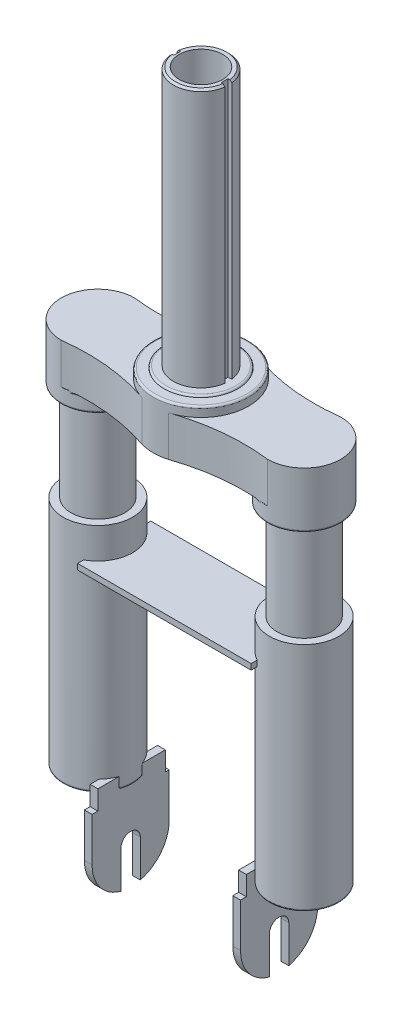
SolidWorks part; units mm, degrees
ref_plane "Front Plane" through (0, 0, 0) normal (0, 0, 1) x (1, 0, 0)
ref_plane "Top Plane" through (0, 0, 0) normal (0, 1, 0) x (1, 0, 0)
ref_plane "Right Plane" through (0, 0, 0) normal (1, 0, 0) x (0, 0, -1)
sketch "Sketch1" plane through (0, 0, 0) normal (0, 0, 1) x (1, 0, 0)
  line L0 (0, -70) -> (0, 70)
  point P4 (0, 0)
  dimension "D1" = 140
sketch "Sketch2" plane through (0, 0, 0) normal (0, 1, 0) x (1, 0, 0)
  circle A0 centre (0, 0) radius 14.3
  circle A1 centre (0, 0) radius 11.3
  dimension "D1" = 28.6
  dimension "D2" = 3
extrude "Boss-Extrude1" add sketch "Sketch2" against normal blind 140
sketch "Sketch3" plane through (0, -140, 0) normal (0, -1, 0) x (1, 0, 0)
  line L0 (-53.5, 0) -> (53.5, 0) construction
  line L5 (-72.5, 24.75) -> (72.5, -24.75) construction
  line L6 (-72.5, -24.75) -> (72.5, 24.75) construction
  line L7 (0, 58.8886) -> (0, -34.6433) construction
  circle A1 centre (0, 0) radius 17.2
  arc A2 (49.4574, -18.5649) -> (49.4574, 18.5649) centre (53.5, 0) ccw
  arc A3 (-49.4574, -18.5649) -> (-49.4574, 18.5649) centre (-53.5, 0) cw
  arc A4 (-8.7282, -23.1599) -> (8.7282, -23.1599) centre (0, 0) ccw
  arc A5 (-53.5, -19) -> (-6.9022, -23.7681) centre (-40.4353, -121.401) cw
  arc A6 (53.5, -19) -> (6.9022, -23.7681) centre (40.4353, -121.401) ccw
  arc A7 (53.5, 19) -> (6.9022, 23.7681) centre (40.4353, 121.401) cw
  arc A8 (-53.5, 19) -> (-6.9022, 23.7681) centre (-40.4353, 121.401) ccw
  arc A9 (8.7282, 23.1599) -> (-8.7282, 23.1599) centre (0, 0) ccw
  circle A10 centre (0, 0) radius 11.3 construction
  point P0 (0, 0)
  point P12 (0, 0)
  dimension "D1" = 103.231
  dimension "D3" = 34.4
  dimension "D4" = 38
  dimension "D5" = 49.5
  dimension "D2" = 6.9022
  dimension "D6" = 8.7282
  dimension "D7" = 72.5
  dimension "D8" = 24.75
  dimension "D9" = 93.5319
  dimension "D10" = 58.8886
extrude "Boss-Extrude4" add sketch "Sketch3" along normal blind 21 separate body contours A7 A9 A8 A3 A5 A4 A6 A2 A1 region at (28.6907, -140, -17.2982)
sketch "Sketch7" plane through (0, -140, 0) normal (0, 1, 0) x (1, 0, 0)
  circle A0 centre (0, 0) radius 24.75
  dimension "D1" = 49.5
extrude "Boss-Extrude5" add sketch "Sketch7" along normal blind 5
fillet "Fillet3" radius 1 1 edges at (0, -135, 24.75)
sketch "Sketch8" plane through (0, -135, 0) normal (0, 1, 0) x (1, 0, 0)
  circle A0 centre (0, 0) radius 19.15
  circle A1 centre (0, 0) radius 14.3 construction
  circle A2 centre (0, 0) radius 14.3
  dimension "D1" = 38.3
extrude "Boss-Extrude6" add sketch "Sketch8" along normal blind 0.9
fillet "Fillet4" radius 1 1 edges at (0, -134.1, 19.15)
sketch "Sketch9" plane through (0, -161, 0) normal (0, -1, 0) x (1, 0, 0)
  line L0 (-72.5, 0) -> (-53.5, 0) construction
  line L1 (0, 31.6889) -> (0, -24.75) construction
  arc A0 (-53.5, 19) -> (-53.5, -19) centre (-53.5, 0) ccw construction
  circle A1 centre (-53.5, 0) radius 19
  arc A2 (-6.9022, -23.7681) -> (6.9022, -23.7681) centre (0, 0) ccw construction
  circle A3 centre (53.5, 0) radius 19
  dimension "D1" = 38
extrude "Boss-Extrude7" add sketch "Sketch9" along normal blind 8.0064
fillet "Fillet5" radius 1 4 edges at (34.5, -161, 0) (53.5, -169.0064, 19) (-34.5, -161, 0) (-53.5, -169.0064, -19)
chamfer "Chamfer1" distance 1 angle 45 1 edges at (0, 0, 14.3)
sketch "Sketch10" plane through (0, -169.0064, 0) normal (0, -1, 0) x (1, 0, 0)
  line L0 (0, 39.8113) -> (0, -36.7225) construction
  circle A0 centre (-53.5, 0) radius 18 construction
  circle A1 centre (-53.5, 0) radius 18 construction
  circle A2 centre (-53.5, 0) radius 14
  circle A3 centre (53.5, 0) radius 14
  dimension "D1" = 28
extrude "Boss-Extrude8" add sketch "Sketch10" along normal blind 51.0064
fillet "Fillet7" radius 1 2 edges at (53.5, -169.0064, 14) (-53.5, -169.0064, -14)
sketch "Sketch11" plane through (0, -220.0128, 0) normal (0, -1, 0) x (1, 0, 0)
  line L0 (0, 38.6993) -> (0, -16.4417) construction
  circle A2 centre (-53.5, 0) radius 18
  circle A3 centre (-53.5, 0) radius 14 construction
  circle A4 centre (53.5, 0) radius 18
  dimension "D1" = 36
extrude "Boss-Extrude9" add sketch "Sketch11" along normal blind 120
fillet "Fillet8" radius 1 2 edges at (53.5, -340.0128, 18) (-53.5, -340.0128, -18)
sketch "Sketch17" plane through (0, 0, 0) normal (0, 0, 1) x (1, 0, 0)
  line L0 (-53.5, -340.0128) -> (53.5, -340.0128) construction
  line L1 (-70.5, -340.0128) -> (-36.5, -340.0128) construction
  line L2 (36.5, -340.0128) -> (70.5, -340.0128) construction
  line L3 (0, -340.0128) -> (0, -319.3084) construction
  line L4 (0, -340.0128) -> (0, -352.1369) construction
  line L5 (-36.5, -352.1369) -> (36.5, -352.1369) construction
  line L6 (36.5, -352.1369) -> (36.5, -330.8903) construction
  line L7 (-36.5, -340.0128) -> (-36.5, -334) construction
  line L8 (-36.5, -352.1369) -> (-36.5, -337.5926)
  point P13 (0, -352.1369)
  dimension "D1" = 73
ref_plane "Plane1" through (36.5, 0, 0) normal (1, 0, 0) x (0, 0, -1)
sketch "Sketch13" plane through (36.5, 0, 0) normal (1, 0, 0) x (0, 0, -1)
  line L1 (-17, -344) -> (-17, -334) construction
  line L6 (-17, -334) -> (18, -334)
  line L17 (-17, -334) -> (18, -334) construction
  line L19 (-17, -344) -> (-17, -334)
  line L20 (18, -334) -> (18, -344)
  line L21 (-20, -344) -> (-17, -344)
  line L23 (-20, -344) -> (-20, -366.6403)
  line L24 (0, -344) -> (0, -386.6403) construction
  line L25 (20, -344) -> (20, -366.6403)
  line L26 (-5.02, -366.6403) -> (-5.02, -386)
  line L27 (5.02, -366.6403) -> (5.02, -386)
  line L28 (18, -344) -> (20, -344)
  arc A3 (5.02, -386) -> (20, -366.6403) centre (0, -366.6403) ccw
  arc A4 (5.02, -366.6403) -> (-5.02, -366.6403) centre (0, -366.6403) ccw
  arc A5 (-20, -366.6403) -> (-5.02, -386) centre (0, -366.6403) ccw
  point P28 (0, -344)
  dimension "D6" = 344
  dimension "D4" = 17
  dimension "D5" = 334
  dimension "D3" = 18
  dimension "D2" = 5.02
  dimension "D1" = 20
  dimension "D7" = 366.6403
extrude "Boss-Extrude14" add sketch "Sketch13" along normal blind 4
mirror "Mirror4" about plane through (0, 0, 0) normal (1, 0, 0) of "Boss-Extrude14"
sketch "Sketch20" plane through (0, 0, 0) normal (0, 0, 1) x (1, 0, 0)
  line L0 (-36.5, -386) -> (0, -386) construction
  line L1 (0, -386) -> (0, -236) construction
  line L2 (-45, -236) -> (45, -236)
  line L3 (-45, -236) -> (-45, -239)
  line L4 (45, -236) -> (45, -239)
  line L5 (-45, -239) -> (45, -239)
  point P8 (0, -236)
  dimension "D1" = 150
  dimension "D2" = 90
  dimension "D3" = 3
  dimension "D4" = 3
extrude "Boss-Extrude15" add sketch "Sketch20" along normal mid plane 38
ref_plane "Plane2" through (14.3, 0, 0) normal (1, 0, 0) x (0, 0, -1)
sketch "Sketch21" plane through (14.3, 0, 0) normal (1, 0, 0) x (0, 0, -1)
  line L0 (-1.7847, -134.1) -> (1.7847, -134.1)
  line L1 (18.155, -134.1) -> (-18.155, -134.1) construction
  line L2 (-1.7847, -134.1) -> (-1.7847, 0)
  line L3 (11.3, 0) -> (-11.3, 0) construction
  line L5 (-14.3, -1) -> (14.3, -1) construction
  line L6 (1.7847, -1) -> (1.7847, -134.1)
  line L7 (1.7847, -1) -> (1.7847, 0)
  line L8 (13.3, 0) -> (-13.3, 0) construction
  line L9 (-1.7847, 0) -> (1.7847, 0)
  point P5 (0, -134.1)
  dimension "D1" = 3.5694
extrude "Cut-Extrude1" cut sketch "Sketch21" against normal blind 2
mirror "Mirror5" about plane through (0, 0, 0) normal (1, 0, 0) of "Cut-Extrude1"
